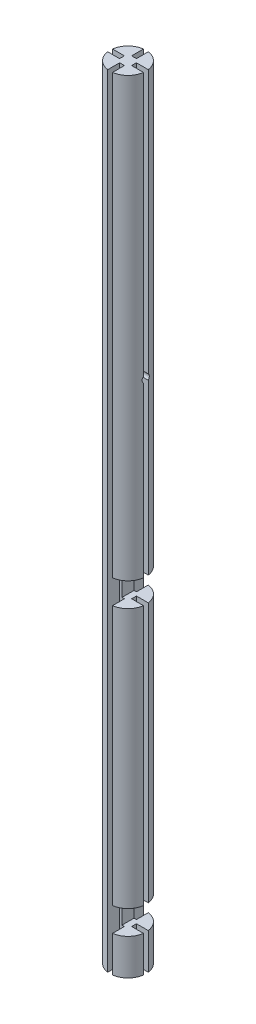
SolidWorks part; units mm, degrees
ref_plane "Front Plane" through (0, 0, 0) normal (0, 0, 1) x (1, 0, 0)
ref_plane "Top Plane" through (0, 0, 0) normal (0, 1, 0) x (1, 0, 0)
ref_plane "Right Plane" through (0, 0, 0) normal (1, 0, 0) x (0, 0, -1)
sketch "Sketch1" plane through (0, 0, 0) normal (0, 1, 0) x (1, 0, 0)
  line L5 (0, 194.8226) -> (0, 75) construction
  line L18 (-10, 74.3303) -> (-10, 25)
  line L19 (-10, 25) -> (10, 25)
  line L20 (10, 74.3303) -> (10, 25)
  line L21 (-29.2048, 0) -> (25.2155, 0) construction
  line L22 (74.3303, -10) -> (25, -10)
  line L23 (74.3303, 10) -> (25, 10)
  line L24 (25, 10) -> (25, -10)
  line L25 (-10, -74.3303) -> (-10, -25)
  line L26 (10, -74.3303) -> (10, -25)
  line L27 (10, -25) -> (-10, -25)
  line L28 (-74.3303, 10) -> (-25, 10)
  line L29 (-74.3303, -10) -> (-25, -10)
  line L30 (-25, -10) -> (-25, 10)
  line L31 (0, 75) -> (0, 25) construction
  line L32 (0, 25) -> (0, -243.8201) construction
  arc A2 (-10, 74.3303) -> (-74.3303, 10) centre (0, 0) ccw
  arc A3 (-74.3303, -10) -> (-10, -74.3303) centre (0, 0) ccw
  arc A4 (10, -74.3303) -> (74.3303, -10) centre (0, 0) ccw
  arc A5 (74.3303, 10) -> (10, 74.3303) centre (0, 0) ccw
  arc A6 (-10, 74.3303) -> (29.2889, 69.0446) centre (0, 0) cw
  point P1 (0, 25)
  point P4 (0, 93.7498)
  point P24 (-100, 0)
  point P29 (0, 0)
  point P30 (0, 0)
  dimension "D1" = 150
  dimension "D2" = 20
  dimension "D3" = 50
  dimension "D4" = 4
extrude "Boss-Extrude2" add sketch "Sketch1" along normal blind 4000 contours A2 L28 L30 L29 A3 L25 L27 L26 A4 L22 L24 L23 A5 L20 L19 L18
sketch "Sketch2" plane through (0, 0, 0) normal (0, 1, 0) x (1, 0, 0)
  line L0 (0, 74.3303) -> (0, -76.7183)
  line L1 (74.3303, 74.3303) -> (74.3303, -76.7183)
  line L2 (74.3303, 74.3303) -> (0, 74.3303)
  line L3 (74.3303, -76.7183) -> (0, -76.7183)
extrude "Cut-Extrude1" cut sketch "Sketch2" along normal mid plane 100 from offset 200
extrude "Cut-Extrude2" cut sketch "Sketch2<2>" against normal mid plane 100 from offset 1380
sketch "Sketch2<2>" plane through (0, 0, 0) normal (0, 1, 0) x (1, 0, 0) same geometry as "Sketch2"
ref_plane "Plane1" through (74.3303, 0, 0) normal (1, 0, 0) x (0, 0, -1)
ref_plane "Plane2" through (0, 0, -74.3303) normal (0, 0, -1) x (-1, 0, 0)
sketch "Sketch3" plane through (74.3303, 0, 0) normal (1, 0, 0) x (0, 0, -1)
  circle A0 centre (0, 2143) radius 15.2
extrude "Cut-Extrude3" cut sketch "Sketch3" against normal up to surface (49.3303 mm away) up to face at (25, 790, 0)
sketch "Sketch4" plane through (0, 0, -74.3303) normal (0, 0, -1) x (-1, 0, 0)
  circle A2 centre (0, 2143) radius 15.2
extrude "Cut-Extrude4" cut sketch "Sketch4" against normal up to surface (49.3303 mm away) up to face at (3.3333, 1193.3333, -25)
sketch "Sketch5" plane through (0, 0, 25) normal (0, 0, 1) x (1, 0, 0)
  line L0 (-74.3303, 4000) -> (-74.3303, 3250)
  line L9 (-74.3303, 4000) -> (-74.3303, 0) construction
  line L10 (-74.3303, 3250) -> (74.3303, 3250)
  line L11 (74.3303, -16.72) -> (74.3303, 16.72) construction
  line L12 (74.3303, 3250) -> (74.3303, 4000)
  line L13 (74.3303, 4000) -> (74.3303, 2154.4473) construction
  line L14 (-74.3303, 4000) -> (74.3303, 4000)
extrude "Cut-Extrude5" cut sketch "Sketch5" against normal through all both and the other way through all
